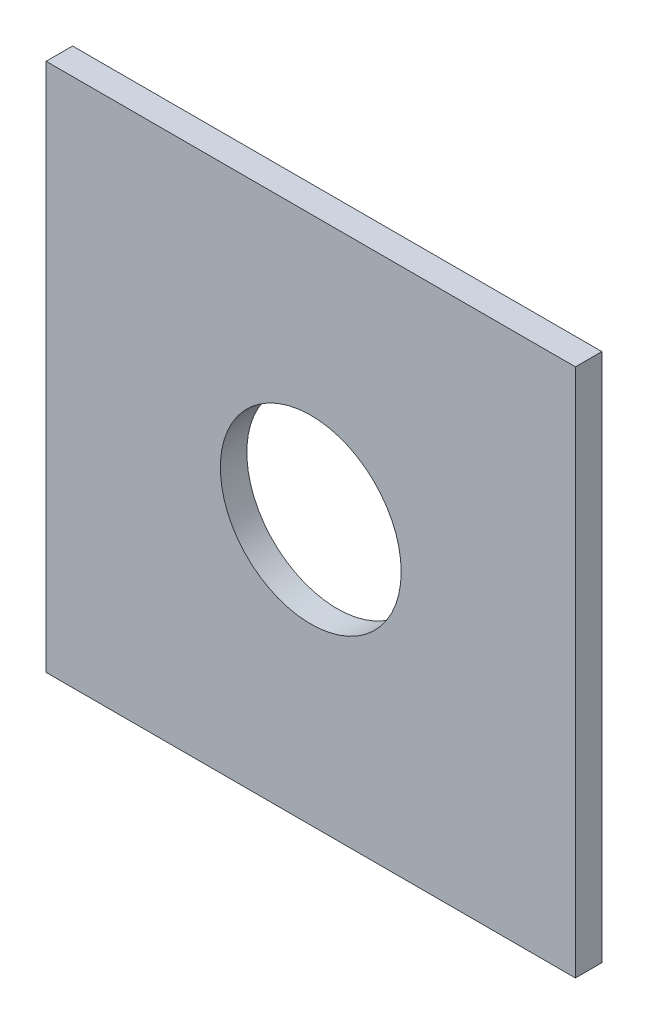
SolidWorks part; units mm, degrees
ref_plane "Front Plane" through (0, 0, 0) normal (0, 0, 1) x (1, 0, 0)
ref_plane "Top Plane" through (0, 0, 0) normal (0, 1, 0) x (1, 0, 0)
ref_plane "Right Plane" through (0, 0, 0) normal (1, 0, 0) x (0, 0, -1)
sketch "Sketch1" plane through (0, 0, 0) normal (0, 0, 1) x (1, 0, 0)
  line L1 (30, -30) -> (-30, -30)
  line L2 (30, -30) -> (30, 30)
  line L3 (30, 30) -> (-30, 30)
  line L4 (-30, -30) -> (-30, 30)
  line L5 (30, -30) -> (-30, 30) construction
  line L6 (30, 30) -> (-30, -30) construction
  point P0 (0, 0)
  dimension "D1" = 60
  dimension "D2" = 60
extrude "Boss-Extrude1" add sketch "Sketch1" along normal blind 3
sketch "Sketch2" plane through (0, 0, 3) normal (0, 0, 1) x (1, 0, 0)
  circle A0 centre (0, 0) radius 10.25
extrude "Cut-Extrude1" cut sketch "Sketch2" against normal through all
